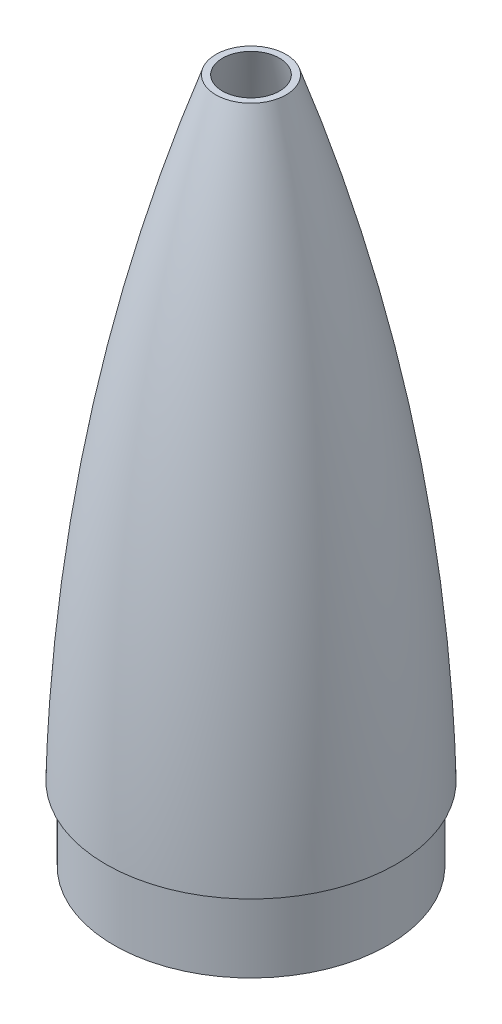
SolidWorks part; units mm, degrees
material "PVB"
ref_plane "Front Plane" through (0, 0, 0) normal (0, 0, 1) x (1, 0, 0)
ref_plane "Top Plane" through (0, 0, 0) normal (0, 1, 0) x (1, 0, 0)
ref_plane "Right Plane" through (0, 0, 0) normal (1, 0, 0) x (0, 0, -1)
sketch "Sketch2" plane through (0, 0, 0) normal (0, 0, 1) x (1, 0, 0)
  line L0 (0, 0) -> (0, 381) construction
  line L1 (-78.359, 0) -> (-70.739, 0)
  line L2 (0, 381) -> (0, 375.92)
  arc A0 (0, 381) -> (-78.359, 0) centre (1014.6868, -26.2452) ccw
  arc A1 (0, 375.92) -> (-70.739, 0) centre (1135.5027, -32.3697) ccw
  dimension "D1" = 381
  dimension "D2" = 5.08
  dimension "D3" = 78.359
  dimension "D4" = 7.62
revolve "Revolve1" add sketch "Sketch2" angle 360 about L2
ref_plane "Plane2" through (0, 381, 0) normal (0, 1, 0) x (1, 0, 0)
sketch "Sketch7" plane through (0, 381, 0) normal (0, 1, 0) x (1, 0, 0)
  circle A0 centre (0, 0) radius 317.5
  dimension "D1" = 635
extrude "Cut-Extrude2" cut sketch "Sketch7" against normal blind 50.8
sketch "Sketch8" plane through (0, 0, 0) normal (0, -1, 0) x (1, 0, 0)
  circle A0 centre (0, 0) radius 70.739
  circle A1 centre (0, 0) radius 74.041
  dimension "D1" = 148.082
extrude "Boss-Extrude1" add sketch "Sketch8" along normal blind 40
